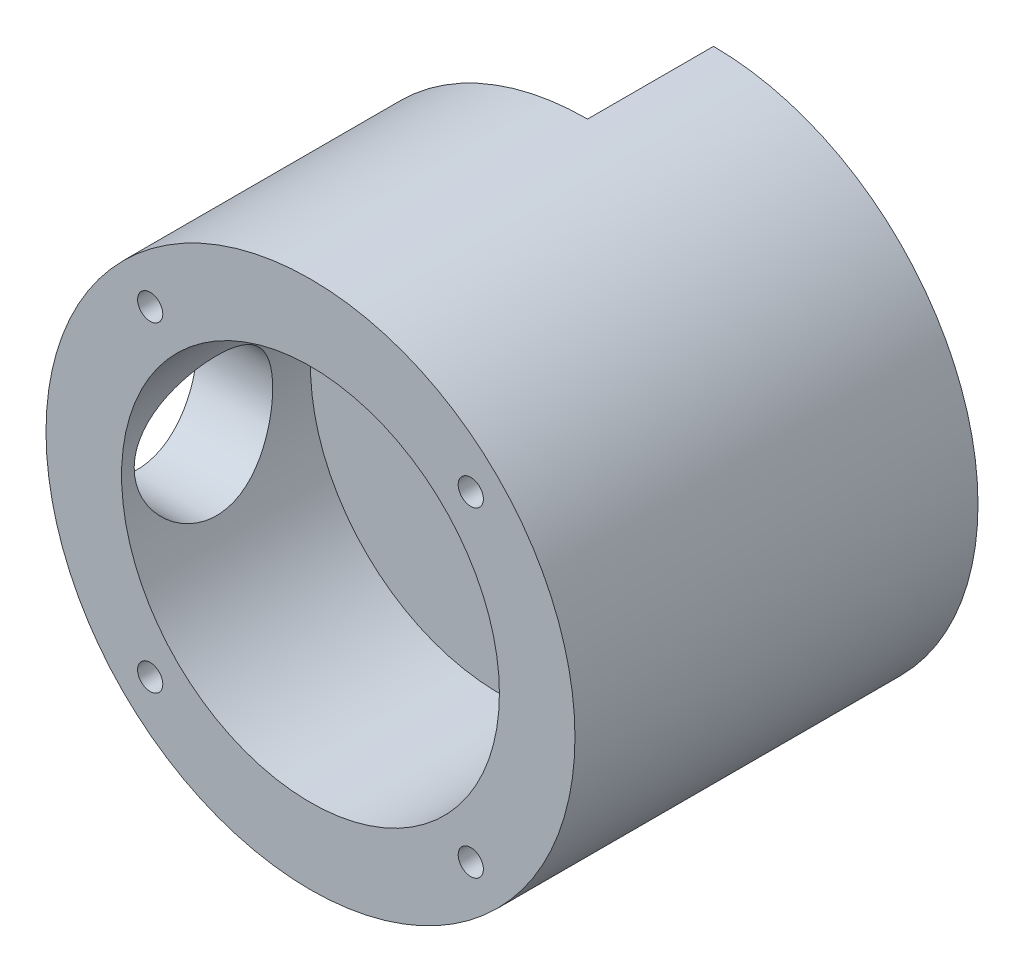
SolidWorks part; units mm, degrees
ref_plane "Front Plane" through (0, 0, 0) normal (0, 0, 1) x (1, 0, 0)
ref_plane "Top Plane" through (0, 0, 0) normal (0, 1, 0) x (1, 0, 0)
ref_plane "Right Plane" through (0, 0, 0) normal (1, 0, 0) x (0, 0, -1)
sketch "Sketch1" plane through (0, 0, 0) normal (0, 0, 1) x (1, 0, 0)
  circle A0 centre (0, 0) radius 10.5
  dimension "D1" = 21
extrude "Boss-Extrude1" add sketch "Sketch1" along normal blind 16
sketch "Sketch2" plane through (0, 0, 16) normal (0, 0, 1) x (1, 0, 0)
  circle A0 centre (0, 0) radius 7.5
  dimension "D1" = 15
extrude "Cut-Extrude1" cut sketch "Sketch2" against normal blind 7.5
sketch "Sketch6" plane through (0, 0, 16) normal (0, 0, 1) x (1, 0, 0)
  line L0 (0, 0) -> (0, 11.163) construction
  line L1 (0, 0) -> (9.3701, 9.3701) construction
  circle A0 centre (6.364, 6.364) radius 0.5
  dimension "D2" = 1
  dimension "D1" = 45
  dimension "D3" = 9
extrude "Cut-Extrude3" cut sketch "Sketch6" against normal blind 7
pattern_circular "CirPattern1" count 4 over 360 about axis through (0, 0, 16) along (0, 0, 1) of "Cut-Extrude3"
sketch "Sketch9" plane through (0, 0, 0) normal (1, 0, 0) x (0, 0, -1)
  line L0 (0, 0) -> (-33.1355, 0) construction
  line L7 (-5, 0) -> (-5, 7.5)
  line L8 (-5, 7.5) -> (-2.5, 7.5)
  line L9 (-2.5, 7.5) -> (-2.5, 5.5)
  line L11 (-2.5, 5.5) -> (0, 5.5)
  line L12 (0, 5.5) -> (0, 0)
  line L14 (-5, 0) -> (0, 0)
  dimension "D1" = 2.5
  dimension "D2" = 5
  dimension "D3" = 5.5
  dimension "D4" = 7.5
revolve "Cut-Revolve1" cut sketch "Sketch9" angle 360 about L0
sketch "Sketch11" plane through (0, 0, 0) normal (1, 0, 0) x (0, 0, -1)
  line L0 (-16, 10.5) -> (-16, -10.5) construction
  circle A0 centre (-12.75, 0) radius 2.75
  dimension "D1" = 5.5
  dimension "D2" = 3.25
extrude "Cut-Extrude6" cut sketch "Sketch11" against normal through all
ref_axis "Axis1" through (0, 0, 16) along (0, 0, -1)
sketch "Sketch13" plane through (0, 0, 0) normal (1, 0, 0) x (0, 0, -1)
  line L0 (-16, -10.5) -> (0, -10.5) construction
  line L1 (0, 10.5) -> (-5, 10.5)
  line L2 (0, 10.5) -> (0, -10.5)
  line L3 (0, -10.5) -> (-5, -10.5)
  line L4 (-5, 10.5) -> (-5, -10.5)
  dimension "D1" = 5
extrude "Cut-Extrude8" cut sketch "Sketch13" against normal through all
sketch "Sketch14" plane through (0, 0, 0) normal (-1, 0, 0) x (0, 0, 1)
  line L0 (0, 5.5) -> (0, 10.5) construction
  line L1 (0, 10.5) -> (5, 10.5) construction
  circle A0 centre (2.5, 9) radius 0.5
  point P2 (0, 0)
  dimension "D1" = 1
  dimension "D2" = 2.5
  dimension "D3" = 1.5
extrude "Cut-Extrude9" cut sketch "Sketch14" against normal blind 2
mirror "Mirror1" about plane through (0, 0, 0) normal (0, 1, 0) of "Cut-Extrude9"
